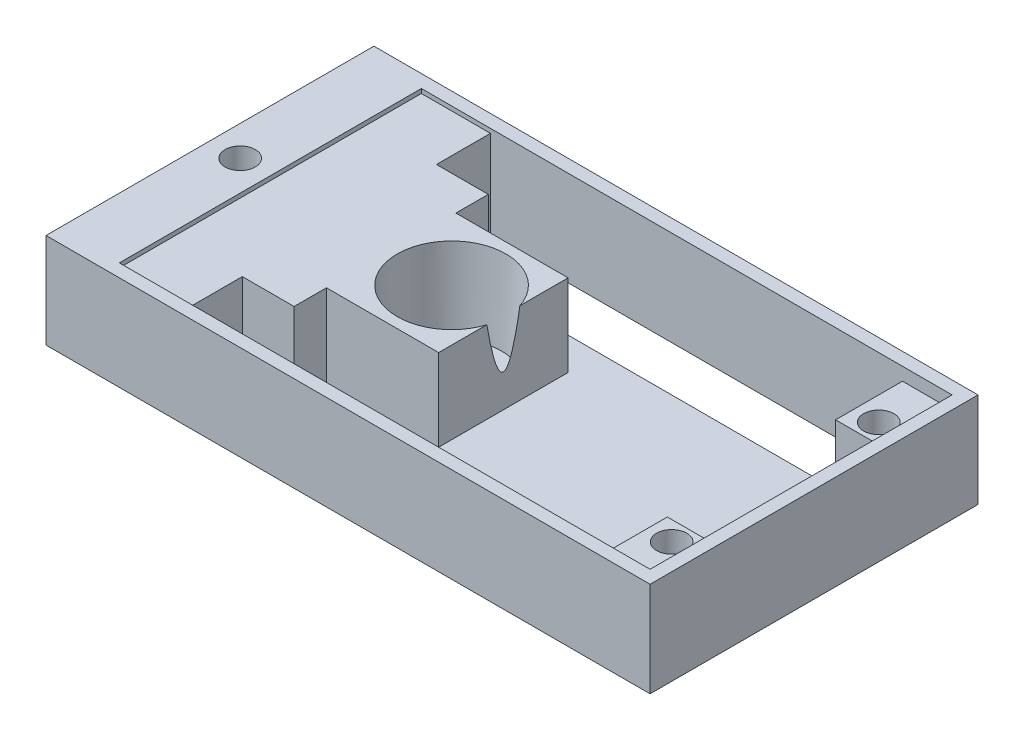
SolidWorks part; units mm, degrees
ref_plane "Front Plane" through (0, 0, 0) normal (0, 0, 1) x (1, 0, 0)
ref_plane "Top Plane" through (0, 0, 0) normal (0, 1, 0) x (1, 0, 0)
ref_plane "Right Plane" through (0, 0, 0) normal (1, 0, 0) x (0, 0, -1)
sketch "Sketch2" plane through (0, 0, 0) normal (0, 1, 0) x (1, 0, 0)
  line L0 (30.5, 12) -> (30.5, -12) construction
  line L1 (-28, 17.5) -> (33.5, 17.5)
  line L2 (-28, 17.5) -> (-28, -17.5)
  line L3 (-28, -17.5) -> (33.5, -17.5)
  line L4 (33.5, 17.5) -> (33.5, -17.5)
  line L5 (33.5, 17.5) -> (27.75, 17.5)
  line L6 (33.5, 17.5) -> (33.5, 9.75)
  line L7 (-35, 19) -> (35, 19)
  line L8 (-35, 19) -> (-35, -19)
  line L9 (-35, -19) -> (35, -19)
  line L10 (35, 19) -> (35, -19)
  line L11 (-35, 19) -> (35, -19) construction
  line L12 (-35, -19) -> (35, 19) construction
  line L13 (33.5, 9.75) -> (27.75, 9.75)
  line L14 (27.75, 17.5) -> (27.75, 9.75)
  line L15 (33.5, -17.5) -> (27.75, -17.5)
  line L16 (33.5, -17.5) -> (33.5, -9.75)
  line L17 (33.5, -9.75) -> (27.75, -9.75)
  line L18 (27.75, -17.5) -> (27.75, -9.75)
  line L19 (-28, 11.25) -> (27.75, 11.25)
  line L20 (27.75, -11.25) -> (-28, -11.25)
  line L21 (-0.125, 11.25) -> (-0.125, -11.25) construction
  circle A0 centre (30.5, 12) radius 1.75
  circle A1 centre (30.5, -12) radius 1.75
  point P6 (0, 0)
  point P22 (30.5, 0)
  point P26 (0, -13.0033)
  point P27 (-0.125, 0)
  point P28 (27.75, 10.5)
  dimension "D8" = 3.5
  dimension "D1" = 38
  dimension "D2" = 70
  dimension "D3" = 35
  dimension "D4" = 7
  dimension "D5" = 1.5
  dimension "D6" = 1.5
  dimension "D7" = 24
  dimension "D9" = 3
  dimension "D10" = 2.75
  dimension "D11" = 2.25
  dimension "D12" = 22.5
extrude "Boss-Extrude1" add sketch "Sketch2" against normal blind 1 contours L10 L7 L8 L9 L1 L4 L3 L2 | L20 L18 L17 L4 L13 L14 L19 L2 | L1 L14 L13 L4 A0 | L18 L3 L4 L17 A1 region at (30.6594, 0, -14.0724) region at (2.3981, 0, 0) region at (30.6594, 0, 14.0724) region at (0, 0, -18.2035)
extrude "Boss-Extrude2" add sketch "Sketch2<3>" along normal blind 10 contours L10 L7 L8 L9 L1 L4 L3 L2 region at (0, 0, -18.2035)
sketch "Sketch2<3>" plane through (0, 0, 0) normal (0, 1, 0) x (1, 0, 0) same geometry as "Sketch2"
extrude "Boss-Extrude3" add sketch "Sketch2<4>" along normal offset from surface (8.5 mm away) 1.5 contours L1 L14 L13 L4 A0 | L18 L3 L4 L17 A1 region at (30.6594, 0, -14.0724) region at (30.6594, 0, 14.0724) up to face at (0, 10, 0)
sketch "Sketch2<4>" plane through (0, 0, 0) normal (0, 1, 0) x (1, 0, 0) same geometry as "Sketch2"
sketch "Sketch3" plane through (0, 10, 0) normal (0, 1, 0) x (1, 0, 0)
  circle A0 centre (30.5, -12) radius 1.75 construction
  circle A1 centre (30.5, 12) radius 1.75 construction
  circle A2 centre (30.5, -12) radius 1.75
  circle A3 centre (30.5, 12) radius 1.75
  circle A4 centre (-31.5, 0) radius 1.75
  point P8 (0, 0)
  dimension "D1" = 31.5
extrude "Cut-Extrude1" cut sketch "Sketch3" against normal through all both and the other way through all
sketch "Sketch4" plane through (0, -1, 0) normal (0, 1, 0) x (1, 0, 0)
  line L0 (-28, 17.5) -> (-28, -17.5) construction
  line L1 (-28, 17.5) -> (-20, 17.5)
  line L2 (-28, 17.5) -> (-28, -17.5)
  line L3 (-28, -17.5) -> (-20, -17.5)
  line L4 (-20, 17.5) -> (-20, 11.25)
  line L5 (-28, 17.5) -> (33.5, 17.5) construction
  line L6 (-20, 11.25) -> (-20, -11.25) construction
  line L7 (-20, 11.25) -> (-14, 11.25)
  line L8 (-20, 11.25) -> (-20, -11.25) construction
  line L9 (-20, -11.25) -> (-14, -11.25)
  line L10 (-14, 11.25) -> (-14, 7.5)
  line L11 (-20, -11.25) -> (-20, -17.5)
  line L12 (-28, -17.5) -> (33.5, -17.5) construction
  line L13 (-14, 7.5) -> (-1, 7.5)
  line L14 (-1, 7.5) -> (-1, -7.5)
  line L15 (-1, -7.5) -> (-14, -7.5)
  line L16 (-14, 7.5) -> (-14, -7.5) construction
  line L17 (-14, -7.5) -> (-14, -11.25)
  point P14 (-1, 0)
  point P20 (-20, 0)
  dimension "D1" = 8
  dimension "D2" = 22.5
  dimension "D3" = 6
  dimension "D4" = 15
  dimension "D5" = 1
extrude "Boss-Extrude4" add sketch "Sketch4" along normal offset from surface (10.5 mm away) 0.5 up to face at (-31.5, 10, 1.75)
sketch "Sketch5" plane through (0, 0, 0) normal (0, 1, 0) x (1, 0, 0)
  circle A0 centre (-7, 0) radius 5.8
  circle A1 centre (-7, 0) radius 2.5
  dimension "D1" = 11.6
  dimension "D3" = 5
  dimension "D2" = 7
extrude "Cut-Extrude2" cut sketch "Sketch5" against normal blind 1 contours A1 region at (-7, 0, 0)
extrude "Cut-Extrude3" cut sketch "Sketch5<3>" along normal through all draft 3 contours A0 draft outward yes
sketch "Sketch5<3>" plane through (0, 0, 0) normal (0, 1, 0) x (1, 0, 0) same geometry as "Sketch5"
